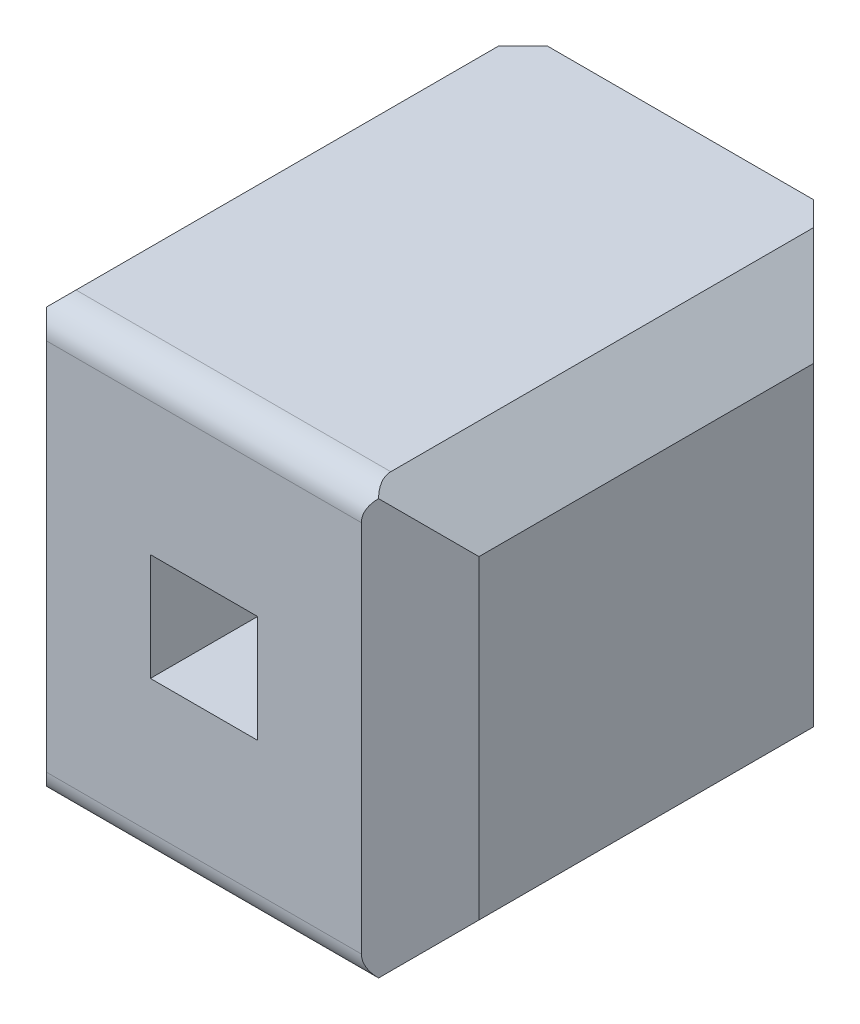
SolidWorks part; units mm, degrees
ref_plane "Front Plane" through (0, 0, 0) normal (0, 0, 1) x (1, 0, 0)
ref_plane "Top Plane" through (0, 0, 0) normal (0, 1, 0) x (1, 0, 0)
ref_plane "Right Plane" through (0, 0, 0) normal (1, 0, 0) x (0, 0, -1)
ref_plane "Plane1" through (0, -0.77, 0) normal (0, -1, 0) x (1, 0, 0)
sketch "Sketch1" plane through (0, -0.77, 0) normal (0, -1, 0) x (1, 0, 0)
  line L0 (29.02, 0.3) -> (29.21, 0.49)
  line L1 (29.21, 0.49) -> (26.67, 0.49)
  line L2 (26.67, 0.49) -> (26.86, 0.3)
  line L3 (26.86, 0.3) -> (29.02, 0.3)
extrude "Boss-Extrude1" add sketch "Sketch1" against normal blind 1.54
sketch "Sketch2" plane through (0, 0.77, 0) normal (0, 1, 0) x (-1, 0, 0)
  line L0 (-26.67, 0.49) -> (-27.1586, 0.0014)
  line L1 (-27.1586, 0.0014) -> (-28.7214, 0.0014)
  line L2 (-28.7214, 0.0014) -> (-29.21, 0.49)
  line L3 (-29.21, 0.49) -> (-26.67, 0.49)
extrude "Boss-Extrude2" add sketch "Sketch2" along normal blind 0.5
sketch "Sketch3" plane through (0, 0, 0.49) normal (0, 0, 1) x (1, 0, 0)
  line L0 (26.67, -0.77) -> (26.67, 1.27)
  line L1 (26.67, 1.27) -> (29.21, 1.27)
  line L2 (29.21, 1.27) -> (29.21, -0.77)
  line L3 (29.21, -0.77) -> (26.67, -0.77)
extrude "Boss-Extrude3" add sketch "Sketch3" along normal blind 2.31
sketch "Sketch4" plane through (0, -0.77, 0) normal (0, -1, 0) x (1, 0, 0)
  line L0 (29.21, 0.49) -> (28.7214, 0.0014)
  line L1 (28.7214, 0.0014) -> (27.1586, 0.0014)
  line L2 (27.1586, 0.0014) -> (26.67, 0.49)
  line L3 (26.67, 0.49) -> (26.67, 2.8)
  line L4 (26.67, 2.8) -> (29.21, 2.8)
  line L5 (29.21, 2.8) -> (29.21, 0.49)
extrude "Boss-Extrude4" add sketch "Sketch4" along normal blind 0.5
sketch "Sketch5" plane through (0, 0, 2.8) normal (0, 0, 1) x (1, 0, 0)
  line L0 (28.255, -0.315) -> (28.255, 0.315)
  line L1 (28.255, 0.315) -> (27.625, 0.315)
  line L2 (27.625, 0.315) -> (27.625, -0.315)
  line L3 (27.625, -0.315) -> (28.255, -0.315)
extrude "Cut-Extrude1" cut sketch "Sketch5" against normal through all
chamfer "Chamfer1" distance 0.3455 angle 45 6 edges at (29.21, 1.27, 1.645) (29.21, 0, 2.8) (29.21, -1.27, 1.645) (26.67, -1.27, 1.645) (26.67, 1.27, 1.645) (26.67, 0, 2.8)
fillet "Fillet1" radius 0.1727 2 edges at (27.94, -1.27, 2.8) (27.94, 1.27, 2.8) tangent propagation no
